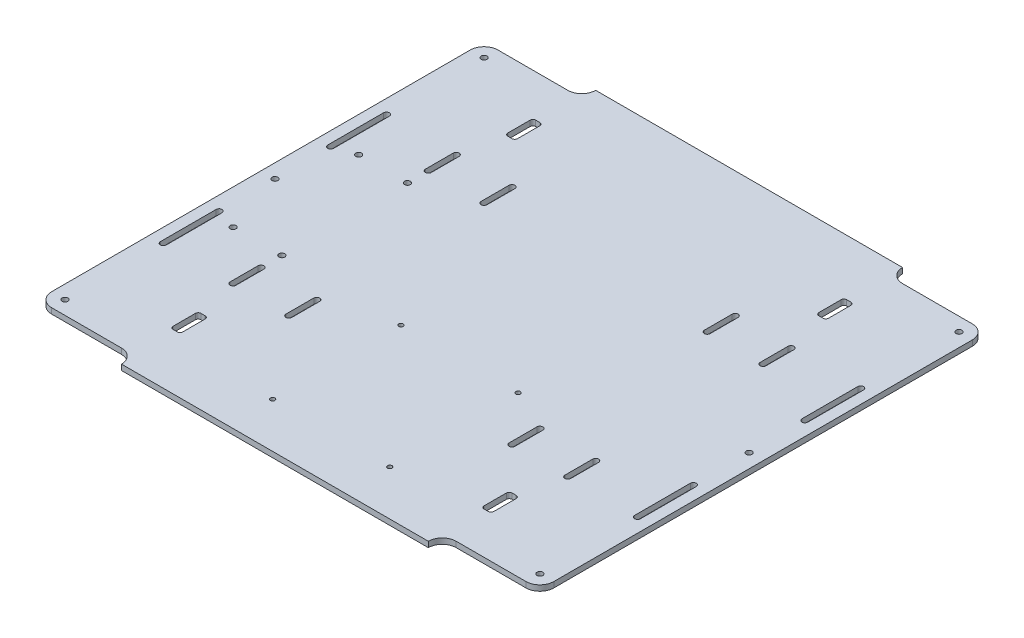
SolidWorks part; units mm, degrees
ref_plane "前视基准面" through (0, 0, 0) normal (0, 0, 1) x (1, 0, 0)
ref_plane "上视基准面" through (0, 0, 0) normal (0, 1, 0) x (1, 0, 0)
ref_plane "右视基准面" through (0, 0, 0) normal (1, 0, 0) x (0, 0, -1)
other "Configuration Table"
sketch "草图1" plane through (0, 0, 0) normal (0, 1, 0) x (1, 0, 0)
  line L1 (-170, -160) -> (170, -160)
  line L2 (-180, -150) -> (-180, 150)
  line L3 (-170, 160) -> (170, 160)
  line L4 (180, -150) -> (180, 150)
  line L5 (-180, -160) -> (-176.8966, -157.2414) construction
  line L6 (-180, 160) -> (-176.8966, 157.2414) construction
  line L8 (176.8966, 157.2414) -> (180, 160) construction
  line L9 (176.8966, -157.2414) -> (180, -160) construction
  arc A0 (170, -160) -> (180, -150) centre (170, -150) ccw
  arc A1 (-180, 150) -> (-170, 160) centre (-170, 150) cw
  arc A2 (-170, -160) -> (-180, -150) centre (-170, -150) cw
  arc A3 (170, 160) -> (180, 150) centre (170, 150) cw
  point P0 (0, 0)
  dimension "D3" = 10
  dimension "D1" = 360
  dimension "D2" = 320
extrude "凸台-拉伸1" add sketch "草图1" along normal mid plane 4
sketch "草图5" plane through (0, 2, 0) normal (0, 1, 0) x (1, 0, 0)
  line L0 (0, 0) -> (0, 142.7283) construction
  line L1 (180, 0) -> (-180, 0) construction
  line L2 (-180, 150) -> (-180, -150) construction
  line L4 (170, 160) -> (-170, 160) construction
  circle A17 centre (80, 80) radius 2.1
  circle A18 centre (120, 80) radius 2.1
  circle A19 centre (-120, 80) radius 2.1
  circle A20 centre (-80, 80) radius 2.1
  circle A23 centre (-80, -80) radius 2.1
  circle A24 centre (-120, -80) radius 2.1
  circle A25 centre (120, -80) radius 2.1
  circle A26 centre (80, -80) radius 2.1
  circle A29 centre (-170, 0) radius 2.1
  circle A30 centre (-170, -40) radius 2.1
  circle A31 centre (-170, -80) radius 2.1
  circle A32 centre (-170, 80) radius 2.1
  circle A33 centre (-170, 40) radius 2.1
  circle A34 centre (170, 40) radius 2.1
  circle A35 centre (170, 80) radius 2.1
  circle A36 centre (170, -80) radius 2.1
  circle A37 centre (170, -40) radius 2.1
  circle A38 centre (170, 0) radius 2.1
  dimension "D2" = 80
  dimension "D1" = 4.2
  dimension "D3" = 10
extrude "切除-拉伸4" cut sketch "草图5" against normal blind 240
sketch "草图6" plane through (0, 2, 0) normal (0, 1, 0) x (1, 0, 0)
  line L0 (170, 160) -> (-170, 160) construction
  line L1 (-180, 150) -> (-180, -150) construction
  line L2 (180, -150) -> (180, 150) construction
  line L3 (-170, -160) -> (170, -160) construction
  circle A0 centre (-170.25, 150.25) radius 2.1
  circle A1 centre (170.25, 150.25) radius 2.1
  circle A2 centre (170.25, -150.25) radius 2.1
  circle A3 centre (-170.25, -150.25) radius 2.1
  dimension "D1" = 4.2
  dimension "D4" = 4.2
  dimension "D6" = 4.2
  dimension "D8" = 4.2
  dimension "D2" = 9.75
  dimension "D3" = 9.75
  dimension "D5" = 9.75
  dimension "D7" = 9.75
  dimension "D9" = 9.75
  dimension "D10" = 9.75
extrude "切除-拉伸5" cut sketch "草图6" against normal blind 10
sketch "草图7" plane through (0, -2, 0) normal (0, -1, 0) x (-1, 0, 0)
  line L0 (180, 150) -> (180, -150) construction
  line L1 (170, -160) -> (-170, -160) construction
  circle A0 centre (145, -110) radius 2.1
  dimension "D1" = 4.2
  dimension "D2" = 35
  dimension "D3" = 50
extrude "切除-拉伸6" cut sketch "草图7" against normal blind 10
sketch "草图8" plane through (0, 2, 0) normal (0, 1, 0) x (1, 0, 0)
  line L25 (-148.8459, -103.0469) -> (-123.0599, -103.0469)
  line L26 (-148.8459, -103.0469) -> (-148.8459, -118.0194)
  line L27 (-148.8459, -118.0194) -> (-123.0599, -118.0194)
  line L28 (-123.0599, -103.0469) -> (-123.0599, -118.0194)
extrude "凸台-拉伸2" add sketch "草图8" against normal blind 4
sketch "草图9" plane through (0, -2, 0) normal (0, -1, 0) x (1, 0, 0)
  line L1 (180, 150) -> (180, -150) construction
  circle A0 centre (50, 137.6322) radius 1.6
  circle A1 centre (50, 45.6322) radius 1.6
  circle A2 centre (-34, 45.6322) radius 1.6
  circle A3 centre (-34, 137.6322) radius 1.6
  dimension "D1" = 3.2
  dimension "D2" = 3.2
  dimension "D3" = 3.2
  dimension "D4" = 3.2
  dimension "D5" = 84
  dimension "D6" = 92
  dimension "D7" = 130
extrude "切除-拉伸7" cut sketch "草图9" against normal blind 10
sketch "草图10" plane through (0, 2, 0) normal (0, 1, 0) x (1, 0, 0)
  line L5 (170, 160) -> (-170, 160) construction
  line L6 (-110, 170) -> (110, 170)
  line L7 (0, 0) -> (-180, 0) construction
  line L8 (-180, 150) -> (-180, -150) construction
  line L13 (-110, 170) -> (-110, 160)
  line L14 (-110, 160) -> (110, 160)
  line L15 (110, 170) -> (110, 160)
  line L16 (-110, 170) -> (110, 160) construction
  line L17 (-110, 160) -> (110, 170) construction
  line L18 (-110, -160) -> (110, -160)
  line L19 (110, -170) -> (110, -160)
  line L20 (-110, -170) -> (110, -170)
  line L21 (-110, -170) -> (-110, -160)
  point P0 (0, 165)
  line M38 (-170, -160) -> (170, -160)
  dimension "D1" = 220
  dimension "D2" = 10
  dimension "D3" = 220
extrude "凸台-拉伸3" add sketch "草图10" against normal blind 4 contours L21 L20 L19 M38 | L15 L14 L13 L6 region at (0, 2, 165)
fillet "圆角1" radius 10 4 edges at (-110, 0, 160) (110, 0, 160) (110, 0, -160) (-110, 0, -160)
sketch "草图13" plane through (0, -2, 0) normal (0, -1, 0) x (1, 0, 0)
  line L0 (-180, -150) -> (-180, 150) construction
  line L1 (0, 0) -> (-180, 0) construction
  circle A0 centre (-155, 45) radius 2.1
  circle A1 centre (-120, 45) radius 2.1
  circle A2 centre (-120, -45) radius 2.1
  circle A3 centre (-155, -45) radius 2.1
  dimension "D1" = 4.2
  dimension "D3" = 4.2
  dimension "D4" = 35
  dimension "D5" = 90
  dimension "D2" = 25
extrude "切除-拉伸8" cut sketch "草图13" against normal blind 10
sketch "草图14" plane through (0, -2, 0) normal (0, -1, 0) x (1, 0, 0)
  line L0 (-170, 160) -> (-120, 160) construction
  line L1 (-180, -150) -> (-180, 150) construction
  line L2 (-120, 100) -> (-120, 140) construction
  line L3 (-115, 112) -> (-115, 128)
  line L4 (-113, 130) -> (-110, 130)
  line L5 (-108, 128) -> (-108, 112)
  line L6 (-110, 110) -> (-113, 110)
  line L7 (0, 0) -> (-180, 0) construction
  line L8 (0, 0) -> (0, 170) construction
  line L9 (-110, 170) -> (110, 170) construction
  line L10 (108, 128) -> (108, 112)
  line L11 (113, 130) -> (110, 130)
  line L12 (115, 112) -> (115, 128)
  line L13 (110, 110) -> (113, 110)
  line L14 (113, -130) -> (110, -130)
  line L15 (115, -112) -> (115, -128)
  line L16 (110, -110) -> (113, -110)
  line L17 (108, -128) -> (108, -112)
  line L18 (-108, -128) -> (-108, -112)
  line L19 (-113, -130) -> (-110, -130)
  line L20 (-115, -112) -> (-115, -128)
  line L21 (-110, -110) -> (-113, -110)
  arc A0 (-108, 112) -> (-110, 110) centre (-110, 112) cw
  arc A1 (-110, 130) -> (-108, 128) centre (-110, 128) cw
  arc A2 (-113, 110) -> (-115, 112) centre (-113, 112) cw
  arc A3 (-115, 128) -> (-113, 130) centre (-113, 128) cw
  arc A4 (110, -110) -> (108, -112) centre (110, -112) ccw
  arc A5 (115, -112) -> (113, -110) centre (113, -112) ccw
  arc A6 (110, -130) -> (108, -128) centre (110, -128) cw
  arc A7 (113, -130) -> (115, -128) centre (113, -128) ccw
  arc A8 (-115, -112) -> (-113, -110) centre (-113, -112) cw
  arc A9 (-113, -130) -> (-115, -128) centre (-113, -128) cw
  arc A10 (-108, -112) -> (-110, -110) centre (-110, -112) ccw
  arc A11 (-108, -128) -> (-110, -130) centre (-110, -128) cw
  arc A12 (115, 112) -> (113, 110) centre (113, 112) cw
  arc A13 (113, 130) -> (115, 128) centre (113, 128) cw
  arc A14 (108, 112) -> (110, 110) centre (110, 112) ccw
  arc A15 (108, 128) -> (110, 130) centre (110, 128) cw
  point P0 (-120, 100)
  point P11 (-120, 120)
  point P12 (-115, 120)
  point P33 (-108, 110)
  point P36 (-108, 130)
  point P39 (-115, 110)
  point P42 (-115, 130)
  point P45 (108, -110)
  point P48 (115, -110)
  point P51 (108, -130)
  point P54 (115, -130)
  point P57 (-115, -110)
  point P60 (-115, -130)
  point P63 (-108, -110)
  point P66 (-108, -130)
  point P69 (115, 110)
  point P72 (115, 130)
  point P75 (108, 110)
  point P78 (108, 130)
  dimension "D7" = 2
  dimension "D8" = 2
  dimension "D1" = 60
  dimension "D2" = 60
  dimension "D3" = 40
  dimension "D4" = 20
  dimension "D5" = 7
  dimension "D6" = 5
extrude "切除-拉伸9" cut sketch "草图14" against normal blind 10
sketch "草图15" plane through (0, 2, 0) normal (0, 1, 0) x (1, 0, 0)
  line L0 (0, 0) -> (180, 0) construction
  line L3 (180, -150) -> (180, 150) construction
  line L5 (0, 0) -> (0, 170) construction
  line L6 (-110, 170) -> (110, 170) construction
  line L7 (-120, 80) -> (-120, 60) construction
  line L16 (-117.9, 80) -> (-117.9, 60)
  line L25 (-122.1, 80) -> (-122.1, 60)
  line L30 (-80, 80) -> (-80, 60) construction
  line L33 (-77.9, 80) -> (-77.9, 60)
  line L36 (-82.1, 80) -> (-82.1, 60)
  line L39 (80, 80) -> (80, 60) construction
  line L42 (77.9, 80) -> (77.9, 60)
  line L45 (170, 80) -> (170, 40) construction
  line L46 (172.1, 80) -> (172.1, 40)
  line L47 (167.9, 80) -> (167.9, 40)
  line L48 (170, -80) -> (170, -40) construction
  line L49 (172.1, -80) -> (172.1, -40)
  line L50 (167.9, -80) -> (167.9, -40)
  line L51 (-170, -80) -> (-170, -40) construction
  line L52 (-172.1, -80) -> (-172.1, -40)
  line L53 (-167.9, -80) -> (-167.9, -40)
  line L54 (-170, 80) -> (-170, 40) construction
  line L55 (-172.1, 80) -> (-172.1, 40)
  line L56 (-167.9, 80) -> (-167.9, 40)
  line L57 (82.1, 80) -> (82.1, 60)
  line L58 (120, 80) -> (120, 60) construction
  line L59 (117.9, 80) -> (117.9, 60)
  line L60 (122.1, 80) -> (122.1, 60)
  line L61 (120, -80) -> (120, -60) construction
  line L62 (117.9, -80) -> (117.9, -60)
  line L63 (122.1, -80) -> (122.1, -60)
  line L64 (80, -80) -> (80, -60) construction
  line L65 (77.9, -80) -> (77.9, -60)
  line L66 (82.1, -80) -> (82.1, -60)
  line L67 (-80, -80) -> (-80, -60) construction
  line L68 (-77.9, -80) -> (-77.9, -60)
  line L69 (-82.1, -80) -> (-82.1, -60)
  line L70 (-120, -80) -> (-120, -60) construction
  line L71 (-117.9, -80) -> (-117.9, -60)
  line L72 (-122.1, -80) -> (-122.1, -60)
  arc A32 (172.1, 80) -> (167.9, 80) centre (170, 80) ccw
  arc A33 (167.9, 40) -> (172.1, 40) centre (170, 40) ccw
  arc A34 (172.1, -80) -> (167.9, -80) centre (170, -80) cw
  arc A35 (167.9, -40) -> (172.1, -40) centre (170, -40) cw
  arc A36 (-172.1, -80) -> (-167.9, -80) centre (-170, -80) ccw
  arc A37 (-167.9, -40) -> (-172.1, -40) centre (-170, -40) ccw
  arc A38 (-172.1, 80) -> (-167.9, 80) centre (-170, 80) cw
  arc A39 (-167.9, 40) -> (-172.1, 40) centre (-170, 40) cw
  arc A40 (-117.9, 80) -> (-122.1, 80) centre (-120, 80) ccw
  arc A41 (-122.1, 60) -> (-117.9, 60) centre (-120, 60) ccw
  arc A42 (-77.9, 80) -> (-82.1, 80) centre (-80, 80) ccw
  arc A43 (-82.1, 60) -> (-77.9, 60) centre (-80, 60) ccw
  arc A44 (77.9, 80) -> (82.1, 80) centre (80, 80) cw
  arc A45 (82.1, 60) -> (77.9, 60) centre (80, 60) cw
  arc A46 (117.9, 80) -> (122.1, 80) centre (120, 80) cw
  arc A47 (122.1, 60) -> (117.9, 60) centre (120, 60) cw
  arc A48 (117.9, -80) -> (122.1, -80) centre (120, -80) ccw
  arc A49 (122.1, -60) -> (117.9, -60) centre (120, -60) ccw
  arc A50 (77.9, -80) -> (82.1, -80) centre (80, -80) ccw
  arc A51 (82.1, -60) -> (77.9, -60) centre (80, -60) ccw
  arc A52 (-77.9, -80) -> (-82.1, -80) centre (-80, -80) cw
  arc A53 (-82.1, -60) -> (-77.9, -60) centre (-80, -60) cw
  arc A54 (-117.9, -80) -> (-122.1, -80) centre (-120, -80) cw
  arc A55 (-122.1, -60) -> (-117.9, -60) centre (-120, -60) cw
  point P7 (-120, 70)
  point P21 (-80, 70)
  point P28 (80, 70)
  point P35 (120, 70)
  point P42 (120, -70)
  point P49 (80, -70)
  point P56 (-80, -70)
  point P63 (-120, -70)
  point P74 (170, 60)
  point P81 (170, -60)
  point P88 (-170, -60)
  point P95 (-170, 60)
  dimension "D1" = 2.1
  dimension "D2" = 20
  dimension "D3" = 2.1
  dimension "D5" = 2.1
  dimension "D4" = 90
extrude "切除-拉伸10" cut sketch "草图15" against normal blind 10
equation "\"2.1、\"=2.62227"
